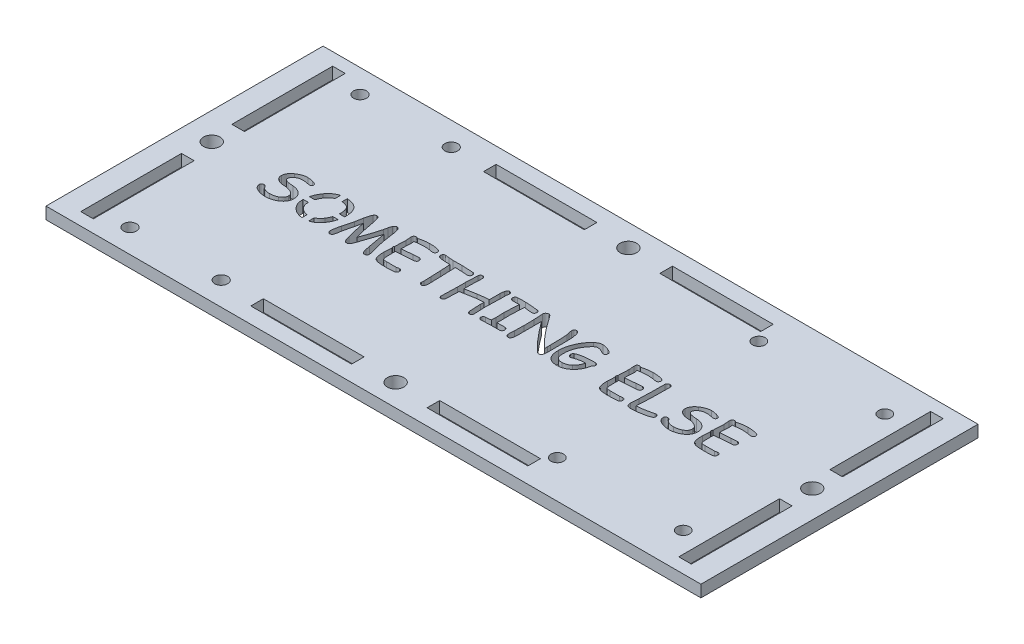
SolidWorks part; units mm, degrees
material "Thornel VCB-20 Carbon Cloth"
ref_plane "Front Plane" through (0, 0, 0) normal (0, 0, 1) x (1, 0, 0)
ref_plane "Top Plane" through (0, 0, 0) normal (0, 1, 0) x (1, 0, 0)
ref_plane "Right Plane" through (0, 0, 0) normal (1, 0, 0) x (0, 0, -1)
sketch "Sketch1" plane through (0, 0, 0) normal (0, 1, 0) x (1, 0, 0)
  line L1 (-82.55, -34.925) -> (82.55, -34.925)
  line L2 (-82.55, -34.925) -> (-82.55, 34.925)
  line L3 (-82.55, 34.925) -> (82.55, 34.925)
  line L4 (82.55, -34.925) -> (82.55, 34.925)
  dimension "D1" = 69.85
  dimension "D2" = 165.1
  dimension "D3" = 34.925
  dimension "D4" = 82.55
extrude "Boss-Extrude1" add sketch "Sketch1" along normal blind 3
sketch "Sketch2" plane through (0, 3, 0) normal (0, 1, 0) x (1, 0, 0)
  line L0 (-82.55, 34.925) -> (-82.55, -34.925) construction
  line L1 (82.55, -34.925) -> (82.55, 34.925) construction
  line L2 (82.55, 34.925) -> (-82.55, 34.925) construction
  line L3 (-82.55, -34.925) -> (82.55, -34.925) construction
  circle A0 centre (-77.47, 29.845) radius 1.5
  circle A1 centre (-77.47, -29.845) radius 1.5
  circle A2 centre (77.47, 29.845) radius 1.5
  circle A3 centre (77.47, -29.845) radius 1.5
  dimension "D1" = 3
  dimension "D2" = 3
  dimension "D3" = 3
  dimension "D4" = 3
  dimension "D5" = 5.08
  dimension "D6" = 5.08
  dimension "D7" = 5.08
  dimension "D8" = 5.08
  dimension "D9" = 5.08
  dimension "D10" = 5.08
  dimension "D11" = 5.08
  dimension "D12" = 5.08
sketch "Sketch3" plane through (0, 3, 0) normal (0, 1, 0) x (1, 0, 0)
  line L0 (-82.55, 34.925) -> (-82.55, -34.925) construction
  line L1 (82.55, -34.925) -> (82.55, 34.925) construction
  line L2 (-82.55, -34.925) -> (82.55, -34.925) construction
  line L3 (82.55, 34.925) -> (-82.55, 34.925) construction
  circle A0 centre (-75.692, 0) radius 2.0828
  circle A1 centre (75.692, 0) radius 2.0828
  circle A2 centre (0, -29.337) radius 2.0828
  circle A3 centre (0, 29.337) radius 2.0828
  point P16 (0, 0)
  point P17 (0, 0)
  point P18 (0, 0)
  dimension "D1" = 6.858
  dimension "D2" = 6.858
  dimension "D3" = 5.588
  dimension "D4" = 5.588
extrude "Cut-Extrude2" cut sketch "Sketch3" against normal blind 5.08
sketch "Sketch4" plane through (0, 3, 0) normal (0, 1, 0) x (1, 0, 0)
  line L0 (-82.55, 34.925) -> (-82.55, -34.925) construction
  line L1 (-44.31, -29) -> (-67.31, -29) construction
  line L2 (-44.31, -29) -> (-44.31, 29) construction
  line L3 (-44.31, 29) -> (-67.31, 29) construction
  line L4 (-67.31, -29) -> (-67.31, 29) construction
  line L5 (-44.31, -29) -> (-67.31, 29) construction
  line L6 (-44.31, 29) -> (-67.31, -29) construction
  circle A0 centre (-67.31, 29) radius 1.625
  circle A1 centre (-44.31, 29) radius 1.625
  circle A2 centre (-44.31, -29) radius 1.625
  circle A3 centre (-67.31, -29) radius 1.625
  point P0 (-55.81, 0)
  point P8 (-35.4796, 29)
  point P10 (0, 0)
  point P11 (-37.5555, -30.15)
  point P13 (-58.4114, -29)
  dimension "D3" = 3.25
  dimension "D1" = 58
  dimension "D2" = 23
  dimension "D4" = 15.24
extrude "Cut-Extrude3" cut sketch "Sketch4" against normal blind 17.78
sketch "Sketch5" plane through (0, 3, 0) normal (0, 1, 0) x (1, 0, 0)
  line L0 (82.55, 34.925) -> (-82.55, 34.925) construction
  line L1 (68.58, -25.4) -> (36.83, -25.4) construction
  line L2 (68.58, -25.4) -> (68.58, 25.4) construction
  line L3 (68.58, 25.4) -> (36.83, 25.4) construction
  line L4 (36.83, -25.4) -> (36.83, 25.4) construction
  line L5 (68.58, -25.4) -> (36.83, 25.4) construction
  line L6 (68.58, 25.4) -> (36.83, -25.4) construction
  line L7 (-82.55, -34.925) -> (82.55, -34.925) construction
  line L8 (82.55, -34.925) -> (82.55, 34.925) construction
  circle A0 centre (68.58, -25.4) radius 1.5875
  circle A2 centre (68.58, 25.4) radius 1.5875
  circle A3 centre (36.83, 25.4) radius 1.5875
  circle A4 centre (36.83, -25.4) radius 1.5875
  point P0 (52.705, 0)
  point P12 (36.9889, 24.6043)
  point P14 (0, 0)
  point P17 (43.6961, 24.6813)
  point P18 (37.4037, -25.4)
  point P20 (68.58, -26.0404)
  dimension "D1" = 9.525
  dimension "D3" = 3.175
  dimension "D2" = 9.525
  dimension "D4" = 31.75
  dimension "D5" = 13.97
extrude "Cut-Extrude4" cut sketch "Sketch5" against normal blind 7.874
sketch "Sketch6" plane through (0, 3, 0) normal (0, 1, 0) x (1, 0, 0)
  line L0 (82.55, 34.925) -> (-82.55, 34.925) construction
  line L1 (-34.925, 27.7495) -> (-9.525, 27.7495)
  line L2 (-34.925, 27.7495) -> (-34.925, 30.9245)
  line L3 (-34.925, 30.9245) -> (-9.525, 30.9245)
  line L4 (-9.525, 27.7495) -> (-9.525, 30.9245)
  line L5 (-34.925, 27.7495) -> (-9.525, 30.9245) construction
  line L6 (-34.925, 30.9245) -> (-9.525, 27.7495) construction
  line L7 (34.925, 30.9245) -> (34.925, 27.7495)
  line L8 (34.925, 30.9245) -> (9.525, 30.9245)
  line L9 (9.525, 30.9245) -> (9.525, 27.7495)
  line L10 (34.925, 27.7495) -> (9.525, 27.7495)
  line L11 (-34.925, -30.9245) -> (-34.925, -27.7495)
  line L12 (-34.925, -27.7495) -> (-9.525, -27.7495)
  line L13 (-9.525, -30.9245) -> (-9.525, -27.7495)
  line L14 (-34.925, -30.9245) -> (-9.525, -30.9245)
  line L15 (34.925, -27.7495) -> (34.925, -30.9245)
  line L16 (34.925, -27.7495) -> (9.525, -27.7495)
  line L17 (9.525, -27.7495) -> (9.525, -30.9245)
  line L18 (34.925, -30.9245) -> (9.525, -30.9245)
  line L19 (-82.55, 34.925) -> (-82.55, -34.925) construction
  line L20 (-76.962, 31.75) -> (-73.787, 31.75)
  line L21 (-76.962, 31.75) -> (-76.962, 6.35)
  line L22 (-76.962, 6.35) -> (-73.787, 6.35)
  line L23 (-73.787, 31.75) -> (-73.787, 6.35)
  line L24 (-76.962, 31.75) -> (-73.787, 6.35) construction
  line L25 (-76.962, 6.35) -> (-73.787, 31.75) construction
  line L26 (-76.962, -6.35) -> (-76.962, -31.75)
  line L27 (-76.962, -6.35) -> (-73.787, -6.35)
  line L28 (-73.787, -6.35) -> (-73.787, -31.75)
  line L29 (-76.962, -31.75) -> (-73.787, -31.75)
  line L30 (-82.55, -34.925) -> (82.55, -34.925) construction
  line L31 (76.962, -31.75) -> (76.962, -6.35)
  line L32 (76.962, -31.75) -> (73.787, -31.75)
  line L33 (73.787, -31.75) -> (73.787, -6.35)
  line L34 (76.962, -6.35) -> (73.787, -6.35)
  line L35 (76.962, 6.35) -> (76.962, 31.75)
  line L36 (76.962, 31.75) -> (73.787, 31.75)
  line L37 (73.787, 6.35) -> (73.787, 31.75)
  line L38 (76.962, 6.35) -> (73.787, 6.35)
  circle A0 centre (0, 29.337) radius 2.0828 construction
  point P0 (-22.225, 29.337)
  point P9 (-75.3745, 19.05)
  point P16 (0, 29.337)
  point P25 (0, 0)
  point P41 (0, 0)
  point P48 (0, 0)
  dimension "D1" = 5.588
  dimension "D2" = 3.175
  dimension "D3" = 25.4
  dimension "D4" = 22.225
  dimension "D7" = 5.588
  dimension "D8" = 3.175
  dimension "D9" = 25.4
  dimension "D10" = 3.175
  dimension "D12" = 3.175
  dimension "D11" = 2
  dimension "D5" = 2
  dimension "D6" = 2
  dimension "D13" = 2
extrude "Cut-Extrude5" cut sketch "Sketch6" against normal blind 10.922
sketch "Sketch7" plane through (0, 3, 0) normal (0, 1, 0) x (1, 0, 0)
  text T0 "SOMETHING ELSE" font "Comic Sans MS" height 9.525
  point P1 (-47.03, 0)
  point P6 (-47.03, 0)
  point P14 (0, 0)
extrude "Cut-Extrude6" cut sketch "Sketch7" against normal blind 10.922
sketch "Sketch8" plane through (0, 3, 0) normal (0, 1, 0) x (1, 0, 0)
  line L0 (-51.8864, -1.053) -> (-47.7613, -1.053)
  line L1 (-51.8864, -1.053) -> (-51.8864, 0.3376)
  line L2 (-51.8864, 0.3376) -> (-47.7613, 0.3376)
  line L3 (-42.0584, -1.053) -> (-42.0584, 0.3376)
  line L4 (-47.7613, -5.9334) -> (-46.1835, -5.9334)
  line L5 (-47.7613, -5.9334) -> (-47.7613, -1.053)
  line L6 (-47.7613, 5.2179) -> (-46.1835, 5.2179)
  line L7 (-46.1835, -5.9334) -> (-46.1835, -1.053)
  line L8 (-46.1835, 0.3376) -> (-42.0584, 0.3376)
  line L9 (-47.7613, 0.3376) -> (-47.7613, 5.2179)
  line L10 (-46.1835, -1.053) -> (-42.0584, -1.053)
  line L11 (-46.1835, 0.3376) -> (-46.1835, 5.2179)
extrude "Boss-Extrude2" add sketch "Sketch8" against normal up to surface (3 mm away) up to face at (-36.3456, 0, 1.0942)
